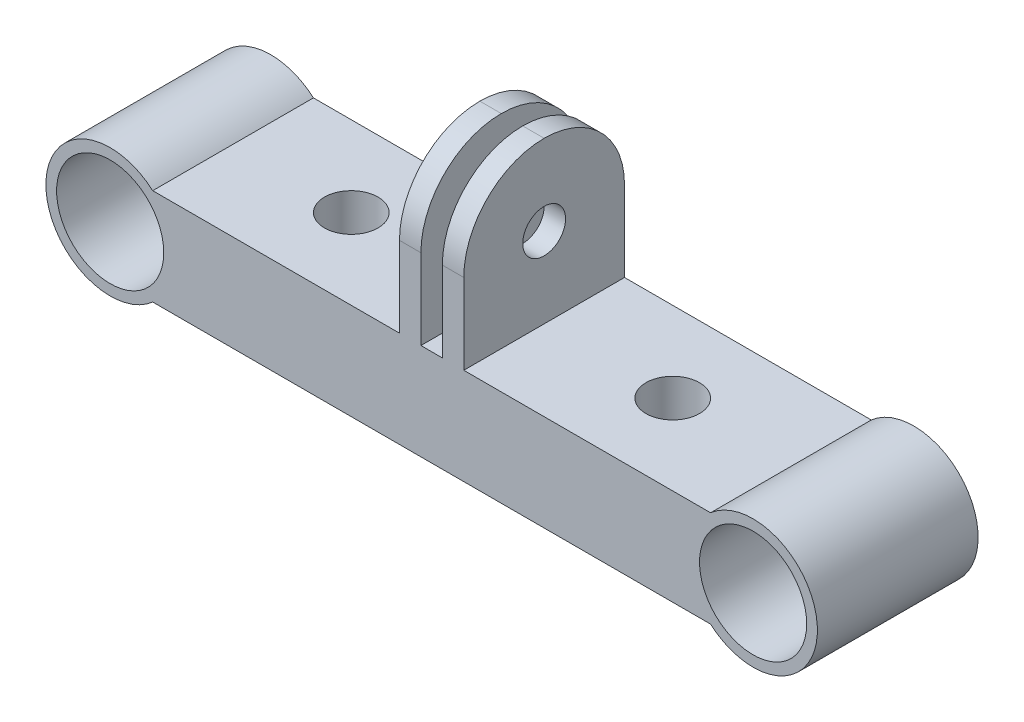
SolidWorks part; units mm, degrees
ref_plane "前视基准面" through (0, 0, 0) normal (0, 0, 1) x (1, 0, 0)
ref_plane "上视基准面" through (0, 0, 0) normal (0, 1, 0) x (1, 0, 0)
ref_plane "右视基准面" through (0, 0, 0) normal (1, 0, 0) x (0, 0, -1)
sketch "草图1" plane through (0, 0, 0) normal (0, 0, 1) x (1, 0, 0)
  line L0 (-26.0314, 4.5) -> (26.0314, 4.5)
  line L1 (0, 0) -> (6.181, 0) construction
  line L2 (-26.0314, -4.5) -> (26.0314, -4.5)
  circle A0 centre (-30, 0) radius 5
  circle A1 centre (30, 0) radius 5
  arc A2 (26.0314, -4.5) -> (26.0314, 4.5) centre (30, 0) ccw
  arc A3 (-26.0314, 4.5) -> (-26.0314, -4.5) centre (-30, 0) ccw
  point P7 (-26.0314, 4.5)
  dimension "D3" = 10
  dimension "D4" = 10
  dimension "D5" = 12
  dimension "D6" = 12
  dimension "D1" = 30
  dimension "D2" = 30
  dimension "D7" = 4.5
extrude "凸台-拉伸1" add sketch "草图1" along normal mid plane 15
sketch "草图2" plane through (0, 0, 7.5) normal (0, 0, 1) x (1, 0, 0)
  line L0 (-3, 4.5) -> (-3, 19.5)
  line L1 (26.0314, 4.5) -> (-26.0314, 4.5) construction
  line L2 (-3, 19.5) -> (3, 19.5)
  line L3 (3, 19.5) -> (3, 4.5)
  line L4 (3, 4.5) -> (-3, 4.5)
  point P6 (0, 4.5)
  dimension "D1" = 6
  dimension "D2" = 15
extrude "凸台-拉伸2" add sketch "草图2" against normal blind 15
fillet "圆角1" radius 7.5 2 edges at (0, 19.5, -7.5) (0, 19.5, 7.5)
sketch "草图3" plane through (0, 0, 7.5) normal (0, 0, 1) x (1, 0, 0)
  line L0 (-3, 4.5) -> (3, 4.5) construction
  line L3 (1, 4.5) -> (-1, 4.5)
  line L4 (1, 4.5) -> (1, 19.5)
  line L5 (1, 19.5) -> (-1, 19.5)
  line L6 (-1, 4.5) -> (-1, 19.5)
  line L7 (-3, 19.5) -> (3, 19.5) construction
  point P0 (0, 8.0286)
  point P13 (0, 4.5)
  dimension "D1" = 2
extrude "切除-拉伸1" cut sketch "草图3" against normal through all
sketch "草图4" plane through (-3, 0, 0) normal (-1, 0, 0) x (0, 0, 1)
  circle A0 centre (0, 12) radius 2
  dimension "D1" = 4
extrude "切除-拉伸2" cut sketch "草图4" against normal blind 15
sketch "草图7" plane through (0, 4.5, 0) normal (0, 1, 0) x (1, 0, 0)
  line L0 (-26.0314, -7.5) -> (-3, -7.5) construction
  line L1 (0, 0) -> (0, -10.4699) construction
  circle A0 centre (-15, 0) radius 2.5
  circle A1 centre (15, 0) radius 2.5
  dimension "D1" = 5
  dimension "D2" = 15
extrude "切除-拉伸3" cut sketch "草图7" against normal through all contours A0 | A1
